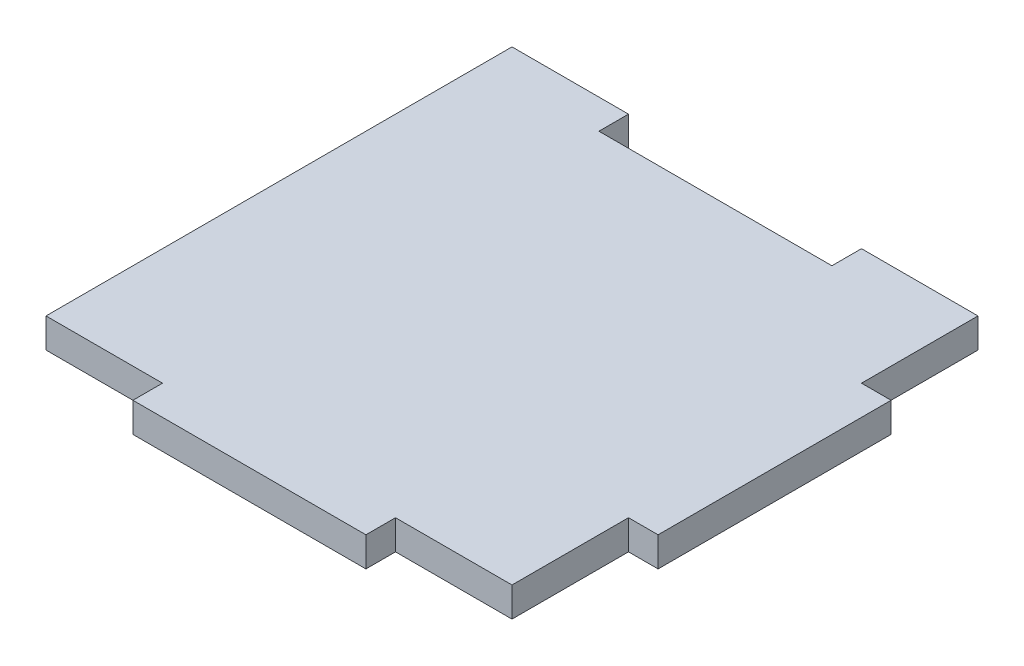
SolidWorks part; units mm, degrees
ref_plane "Front Plane" through (0, 0, 0) normal (0, 0, 1) x (1, 0, 0)
ref_plane "Top Plane" through (0, 0, 0) normal (0, 1, 0) x (1, 0, 0)
ref_plane "Right Plane" through (0, 0, 0) normal (1, 0, 0) x (0, 0, -1)
sketch "Sketch1" plane through (0, 0, 0) normal (0, 1, 0) x (1, 0, 0)
  line L1 (-25, -25) -> (25, -25)
  line L2 (-25, -25) -> (-25, 25)
  line L3 (-25, 25) -> (25, 25)
  line L4 (25, -25) -> (25, 25)
  line L5 (-25, -25) -> (25, 25) construction
  line L6 (-25, 25) -> (25, -25) construction
  point P0 (0, 0)
  dimension "D1" = 50
  dimension "D2" = 50
extrude "Boss-Extrude1" add sketch "Sketch1" along normal blind 3.175
sketch "Sketch3" plane through (0, 3.175, 0) normal (0, 1, 0) x (1, 0, 0)
  line L0 (25, -25) -> (25, 25) construction
  line L1 (25, -25) -> (25, 25)
  line L2 (28.175, 12.5) -> (28.175, 25) construction
  line L3 (25, 12.5) -> (28.175, 12.5)
  line L4 (25, 12.5) -> (25, -12.5)
  line L5 (25, -12.5) -> (28.175, -12.5)
  line L6 (28.175, 12.5) -> (28.175, -12.5)
  line L7 (28.175, -12.5) -> (28.175, -25) construction
  line L8 (25, 25) -> (-25, 25) construction
  line L9 (-25, -25) -> (25, -25) construction
  line L10 (-25, -25) -> (25, -25)
  line L11 (12.5, -25) -> (12.5, -28.175)
  line L12 (12.5, -25) -> (-12.5, -25)
  line L13 (-12.5, -25) -> (-12.5, -28.175)
  line L14 (12.5, -28.175) -> (-12.5, -28.175)
  line L15 (12.5, -28.175) -> (25, -28.175) construction
  line L16 (-12.5, -28.175) -> (-25, -28.175) construction
  line L17 (-25, 25) -> (-25, -25) [skipped]
  line L18 (-25, -12.5) -> (-28.175, -12.5) [skipped]
  line L19 (-25, -12.5) -> (-25, 12.5) [skipped]
  line L20 (-25, 12.5) -> (-28.175, 12.5) [skipped]
  line L21 (-28.175, -12.5) -> (-28.175, 12.5) [skipped]
  line L22 (-28.175, -12.5) -> (-28.175, -25) construction
  line L23 (-28.175, 12.5) -> (-28.175, 25) construction
  line L24 (25, 25) -> (-25, 25) [skipped]
  line L25 (-12.5, 25) -> (-12.5, 28.175) [skipped]
  line L26 (-12.5, 25) -> (12.5, 25) [skipped]
  line L27 (12.5, 25) -> (12.5, 28.175) [skipped]
  line L28 (-12.5, 28.175) -> (12.5, 28.175) [skipped]
  line L29 (-12.5, 28.175) -> (-25, 28.175) construction
  line L30 (12.5, 28.175) -> (25, 28.175) construction
  point P6 (0, 0)
  point P41 (0, 0)
  dimension "D1" = 3.175
  dimension "D2" = 25
  dimension "D3" = 4
extrude "Boss-Extrude3" add sketch "Sketch3" against normal up to surface (3.175 mm away) contours L14 L13 L12 L11 | L6 L5 L4 L3 up to face at (0, 0, 0)
sketch "Sketch4" plane through (0, 3.175, 0) normal (0, 1, 0) x (1, 0, 0)
  line L0 (-12.5, -25) -> (-12.5, 25) construction
  line L1 (25, 25) -> (-25, 25) construction
  line L2 (12.5, -25) -> (12.5, 25) construction
  line L4 (-12.5, 25) -> (12.5, 25)
  line L5 (-12.5, 25) -> (-12.5, 21.825)
  line L6 (-12.5, 21.825) -> (12.5, 21.825)
  line L7 (12.5, 25) -> (12.5, 21.825)
  dimension "D1" = 3.175
extrude "Cut-Extrude1" cut sketch "Sketch4" against normal blind 3.175
